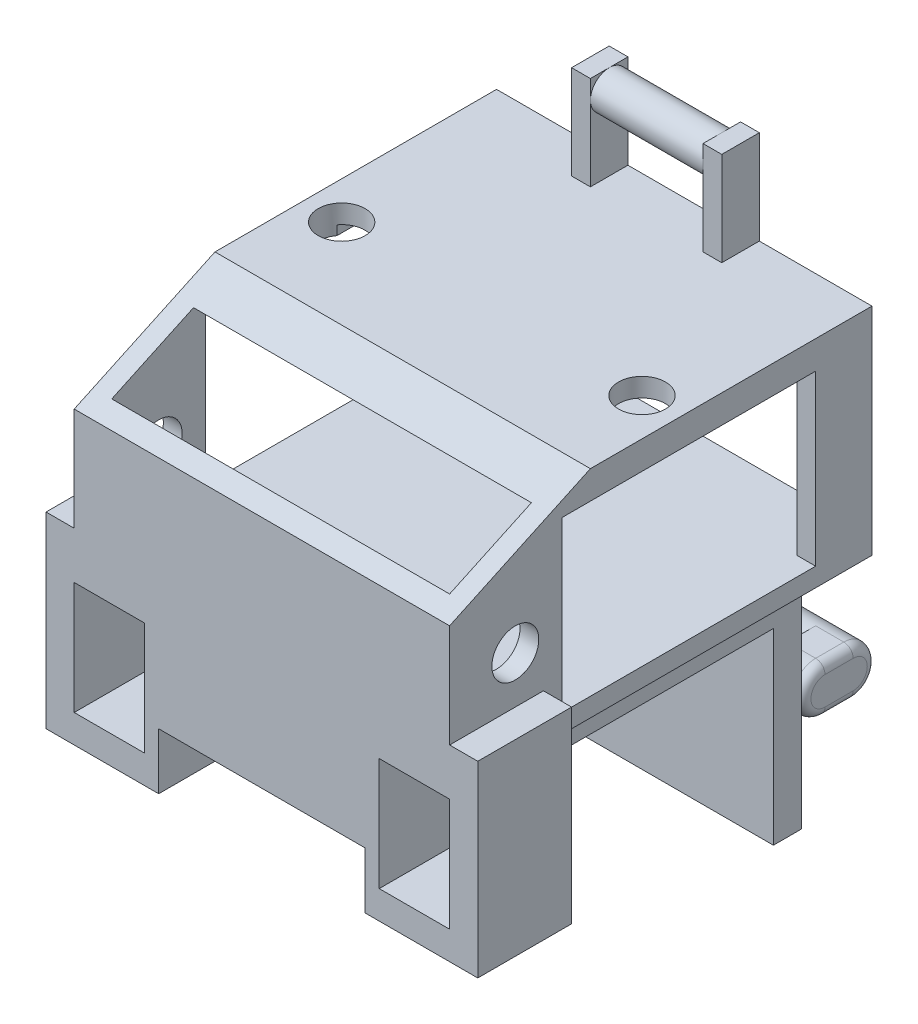
SolidWorks part; units mm, degrees
ref_plane "正面" through (0, 0, 0) normal (0, 0, 1) x (1, 0, 0)
ref_plane "平面" through (0, 0, 0) normal (0, 1, 0) x (1, 0, 0)
ref_plane "右側面" through (0, 0, 0) normal (1, 0, 0) x (0, 0, -1)
sketch "ｽｹｯﾁ1" plane through (0, 0, 0) normal (0, 1, 0) x (1, 0, 0)
  line L1 (0, 0) -> (25, 0)
  line L2 (0, 0) -> (0, 42)
  line L3 (0, 42) -> (25, 42)
  line L4 (25, 0) -> (25, 42)
  dimension "D1" = 25
  dimension "D2" = 42
extrude "ﾎﾞｽ - 押し出し1" add sketch "ｽｹｯﾁ1" along normal blind 9
sketch "ｽｹｯﾁ2" plane through (0, 0, -42) normal (0, 0, -1) x (-1, 0, 0)
  line L1 (-25, 9) -> (0, 9)
  line L2 (-25, 9) -> (-25, -20)
  line L3 (-25, -20) -> (0, -20)
  line L4 (0, 9) -> (0, -20)
  dimension "D1" = 29
extrude "ﾎﾞｽ - 押し出し2" add sketch "ｽｹｯﾁ2" along normal blind 3
sketch "ｽｹｯﾁ3" plane through (0, 9, 0) normal (0, 1, 0) x (1, 0, 0)
  line L1 (-7.5, 0) -> (32.5, 0)
  line L2 (-7.5, 0) -> (-7.5, 45)
  line L3 (-7.5, 45) -> (32.5, 45)
  line L4 (32.5, 0) -> (32.5, 45)
  line L5 (0, 0) -> (25, 0) construction
  line L6 (0, 45) -> (25, 45) construction
  line L7 (0, 45) -> (0, 0) construction
  dimension "D1" = 40
  dimension "D2" = 7.5
extrude "ﾎﾞｽ - 押し出し3" add sketch "ｽｹｯﾁ3" along normal blind 23
sketch "ｽｹｯﾁ4" plane through (0, 0, -45) normal (0, 0, -1) x (-1, 0, 0)
  line L0 (-32.5, 32) -> (7.5, 32) construction
  line L1 (5.5, 30) -> (-30.5, 30)
  line L2 (5.5, 30) -> (5.5, 11)
  line L3 (5.5, 11) -> (-30.5, 11)
  line L4 (-30.5, 30) -> (-30.5, 11)
  line L5 (7.5, 32) -> (7.5, 9) construction
  line L6 (-32.5, 32) -> (-32.5, 9) construction
  line L7 (0, 9) -> (7.5, 9) construction
  dimension "D1" = 2
  dimension "D2" = 2
  dimension "D3" = 2
  dimension "D4" = 2
extrude "ｶｯﾄ - 押し出し1" cut sketch "ｽｹｯﾁ4" against normal blind 43
sketch "ｽｹｯﾁ6" plane through (32.5, 0, 0) normal (1, 0, 0) x (0, 0, -1)
  line L1 (0, -6) -> (10, -6)
  line L2 (0, -6) -> (0, 14)
  line L3 (0, 14) -> (10, 14)
  line L4 (10, -6) -> (10, 14)
  line L5 (0, 9) -> (45, 9) construction
  line L6 (0, 32) -> (0, 9) construction
  dimension "D1" = 10
  dimension "D2" = 20
  dimension "D4" = 15
extrude "ﾎﾞｽ - 押し出し4" add sketch "ｽｹｯﾁ6" along normal blind 3
sketch "ｽｹｯﾁ7" plane through (0, -6, 0) normal (0, -1, 0) x (1, 0, 0)
  line L0 (35.5, 0) -> (32.5, 0) construction
  line L1 (32.5, -10) -> (23.5, -10)
  line L2 (32.5, -10) -> (32.5, 0)
  line L3 (32.5, 0) -> (23.5, 0)
  line L4 (23.5, -10) -> (23.5, 0)
  dimension "D1" = 9
extrude "ﾎﾞｽ - 押し出し5" add sketch "ｽｹｯﾁ7" against normal blind 3
ref_plane "平面1" through (12.5, 0, 0) normal (1, 0, 0) x (0, 0, -1)
mirror "ﾐﾗｰ1" about plane through (12.5, 0, 0) normal (1, 0, 0) of "ﾎﾞｽ - 押し出し4", "ﾎﾞｽ - 押し出し5"
sketch "ｽｹｯﾁ8" plane through (0, 32, 0) normal (0, 1, 0) x (1, 0, 0)
  line L0 (12.5, -15.95) -> (12.5, 15.95) construction
  line L1 (4.5, 45) -> (6.5, 45)
  line L2 (4.5, 45) -> (4.5, 41)
  line L3 (4.5, 41) -> (6.5, 41)
  line L4 (6.5, 45) -> (6.5, 41)
  line L5 (20.5, 41) -> (18.5, 41)
  line L6 (18.5, 45) -> (18.5, 41)
  line L7 (20.5, 45) -> (18.5, 45)
  line L8 (20.5, 45) -> (20.5, 41)
  line L9 (32.5, 45) -> (-7.5, 45) construction
  dimension "D1" = 4
  dimension "D2" = 2
  dimension "D3" = 12
extrude "ﾎﾞｽ - 押し出し6" add sketch "ｽｹｯﾁ8" along normal blind 10
sketch "ｽｹｯﾁ9" plane through (6.5, 0, 0) normal (1, 0, 0) x (0, 0, -1)
  line L0 (41, 42) -> (41, 32) construction
  line L1 (41, 42) -> (45, 42) construction
  circle A0 centre (43, 40) radius 2
  dimension "D1" = 4
  dimension "D2" = 2
  dimension "D3" = 2
extrude "ﾎﾞｽ - 押し出し7" add sketch "ｽｹｯﾁ9" along normal up to next
sketch "ｽｹｯﾁ10" plane through (-7.5, 0, 0) normal (-1, 0, 0) x (0, 0, 1)
  line L0 (-45, 9) -> (-10, 9) construction
  line L1 (0, 32) -> (0, 14) construction
  circle A0 centre (-7, 19) radius 2.5
  dimension "D1" = 5
  dimension "D2" = 10
  dimension "D3" = 7
extrude "ｶｯﾄ - 押し出し2" cut sketch "ｽｹｯﾁ10" against normal through all
sketch "ｽｹｯﾁ11" plane through (0, 0, -45) normal (0, 0, -1) x (-1, 0, 0)
  line L1 (-25, -20) -> (0, -20) construction
  line L2 (-12.5, 15.95) -> (-12.5, -15.95) construction
  circle A0 centre (-12.5, -10) radius 2.5
  dimension "D1" = 5
  dimension "D2" = 10
extrude "ﾎﾞｽ - 押し出し8" add sketch "ｽｹｯﾁ11" along normal blind 9
sketch "ｽｹｯﾁ12" plane through (12.5, 0, 0) normal (1, 0, 0) x (0, 0, -1)
  line L0 (45, -12.5) -> (45, -7.5) construction
  line L2 (45, -12.5) -> (54, -12.5) construction
  circle A0 centre (52, -10) radius 2.5
  dimension "D1" = 5
  dimension "D2" = 7
  dimension "D3" = 2.5
extrude "ﾎﾞｽ - 押し出し9" add sketch "ｽｹｯﾁ12" along normal blind 7
sketch "ｽｹｯﾁ13" plane through (19.5, 0, 0) normal (1, 0, 0) x (0, 0, -1)
  line L0 (52, -10) -> (49, -10) construction
  line L1 (52, -12.5) -> (49, -12.5)
  line L2 (52, -7.5) -> (49, -7.5)
  arc A0 (52, -12.5) -> (52, -7.5) centre (52, -10) ccw
  arc A1 (49, -7.5) -> (49, -12.5) centre (49, -10) ccw
  circle A2 centre (52, -10) radius 2.5 construction
  point P2 (50.5, -10)
  dimension "D1" = 2.5
  dimension "D2" = 3
extrude "ﾎﾞｽ - 押し出し10" add sketch "ｽｹｯﾁ13" along normal blind 4
fillet "ﾌｨﾚｯﾄ1" radius 1 4 edges at (23.5, -12.5, -50.5) (23.5, -10, -46.5) (23.5, -7.5, -50.5) (23.5, -10, -54.5)
mirror "ﾐﾗｰ2" about plane through (12.5, 0, 0) normal (1, 0, 0) of "ﾌｨﾚｯﾄ1", "ﾎﾞｽ - 押し出し10", "ﾎﾞｽ - 押し出し9"
sketch "ｽｹｯﾁ14" plane through (-7.5, 0, 0) normal (-1, 0, 0) x (0, 0, 1)
  line L0 (-15, 32) -> (0, 25)
  line L1 (-45, 32) -> (0, 32) construction
  line L2 (0, 32) -> (0, 14) construction
  line L3 (0, 25) -> (0, 32)
  line L4 (0, 32) -> (-15, 32)
  dimension "D1" = 15
  dimension "D2" = 7
extrude "ｶｯﾄ - 押し出し3" cut sketch "ｽｹｯﾁ14" against normal through all
sketch "ｽｹｯﾁ15" plane through (-7.5, 0, 0) normal (-1, 0, 0) x (0, 0, 1)
  line L0 (-45, 9) -> (-53, 32)
  line L1 (-53, 32) -> (-45, 32)
  line L2 (-45, 32) -> (-45, 9)
  dimension "D1" = 8
sketch "ｽｹｯﾁ19" plane through (30.5, 0, 0) normal (-1, 0, 0) x (0, 0, 1)
  line L0 (-2, 11) -> (-45, 11) construction
  line L1 (-39, 11) -> (-12, 11)
  line L2 (-39, 11) -> (-39, 29)
  line L3 (-39, 29) -> (-12, 29)
  line L4 (-12, 11) -> (-12, 29)
  line L5 (-2, 25.9333) -> (-2, 11) construction
  dimension "D1" = 27
  dimension "D2" = 10
  dimension "D3" = 18
extrude "ｶｯﾄ - 押し出し5" cut sketch "ｽｹｯﾁ19" against normal through all both and the other way through all
sketch "ｽｹｯﾁ20" plane through (0, 32, 0) normal (0, 1, 0) x (1, 0, 0)
  line L0 (-7.5, 45) -> (-7.5, 15) construction
  line L1 (32.5, 15) -> (32.5, 45) construction
  line L4 (18.5, 41) -> (20.5, 41) construction
  line L5 (4.5, 41) -> (6.5, 41) construction
  circle A0 centre (-3.5, 24.5) radius 2.5
  circle A1 centre (28.5, 24.5) radius 2.5
  dimension "D1" = 5
  dimension "D2" = 5
  dimension "D3" = 4
  dimension "D4" = 4
  dimension "D5" = 16.5
  dimension "D6" = 16.5
extrude "ｶｯﾄ - 押し出し6" cut sketch "ｽｹｯﾁ20" against normal blind 10 and the other way through all
sketch "ｽｹｯﾁ21" plane through (0, 30, 0) normal (0, -1, 0) x (1, 0, 0)
  line L0 (-5.5, -45) -> (30.5, -45) construction
  line L1 (-5.5, -10.7143) -> (-5.5, -23) construction
  line L2 (22.5, -45) -> (19.5, -45)
  line L3 (22.5, -45) -> (22.5, -40)
  line L4 (22.5, -40) -> (19.5, -40)
  line L5 (19.5, -45) -> (19.5, -40)
  line L6 (5.5, -45) -> (2.5, -45)
  line L7 (5.5, -45) -> (5.5, -40)
  line L8 (5.5, -40) -> (2.5, -40)
  line L9 (2.5, -45) -> (2.5, -40)
  dimension "D1" = 3
  dimension "D2" = 5
  dimension "D3" = 3
  dimension "D4" = 5
  dimension "D5" = 8
  dimension "D6" = 8
sketch "ｽｹｯﾁ23" plane through (23.5, 0, 0) normal (-1, 0, 0) x (0, 0, 1)
  line L0 (0, 0) -> (-42, 0) construction
  line L1 (-10, -3) -> (0, -3)
  line L2 (-10, -3) -> (-10, 0)
  line L3 (-10, 0) -> (0, 0)
  line L4 (0, -3) -> (0, 0)
  line L5 (0, 25) -> (0, 14) construction
extrude "ﾎﾞｽ - 押し出し13" add sketch "ｽｹｯﾁ23" against normal blind 1.5
mirror "ﾐﾗｰ3" about plane through (12.5, 0, 0) normal (1, 0, 0) of "ﾎﾞｽ - 押し出し13"
